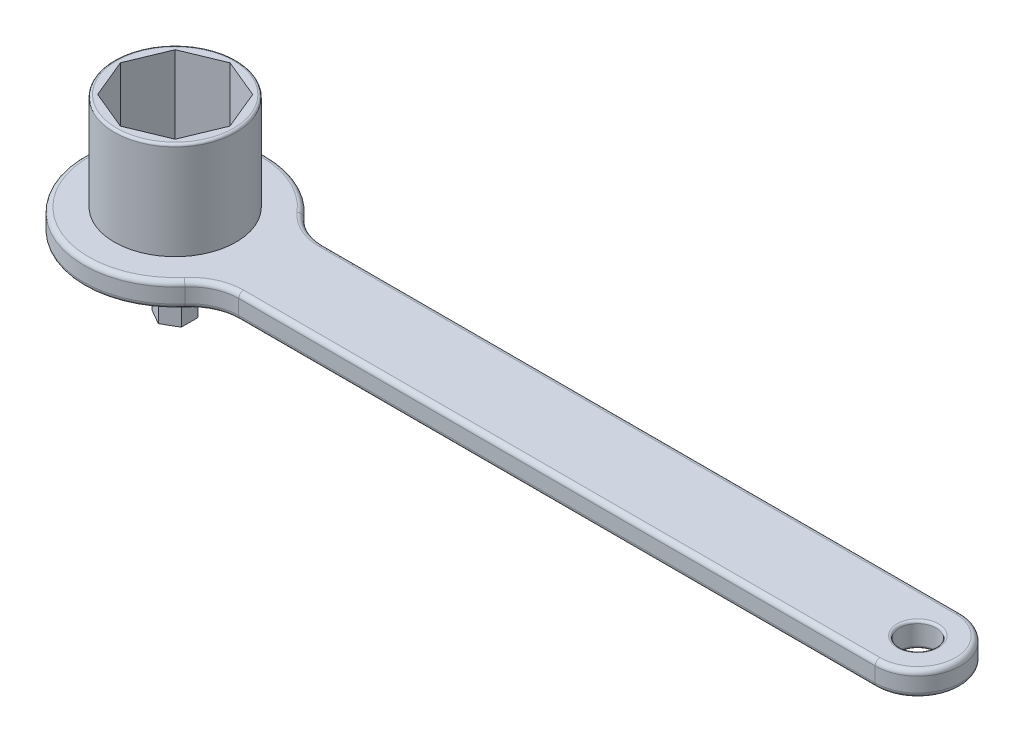
SolidWorks part; units mm, degrees
ref_plane "Front Plane" through (0, 0, 0) normal (0, 0, 1) x (1, 0, 0)
ref_plane "Top Plane" through (0, 0, 0) normal (0, 1, 0) x (1, 0, 0)
ref_plane "Right Plane" through (0, 0, 0) normal (1, 0, 0) x (0, 0, -1)
sketch "Sketch1" plane through (0, 0, 0) normal (0, 1, 0) x (1, 0, 0)
  line L0 (-152.4, 0) -> (152.4, 0) construction
  line L1 (152.4, 17.5) -> (-108.811, 17.5)
  line L2 (152.4, -17.5) -> (-108.811, -17.5)
  arc A0 (-123.9724, 24.4565) -> (-123.9724, -24.4565) centre (-152.4, 0) ccw
  arc A1 (152.4, -17.5) -> (152.4, 17.5) centre (152.4, 0) ccw
  arc A2 (-108.811, -17.5) -> (-123.9724, -24.4565) centre (-108.811, -37.5) ccw
  arc A3 (-108.811, 17.5) -> (-123.9724, 24.4565) centre (-108.811, 37.5) cw
  circle A4 centre (152.4, 0) radius 7.5
  circle A5 centre (-152.4, 0) radius 25
  dimension "D2" = 75
  dimension "D3" = 35
  dimension "D4" = 20
  dimension "D5" = 15
  dimension "D6" = 50
  dimension "D1" = 304.8
extrude "Boss-Extrude1" add sketch "Sketch1" against normal blind 10 contours A5 | L1 A3 A0 A2 L2 A1 A5 A4 region at (-12.9438, 0, 0) region at (-152.4, 0, 0)
extrude "Boss-Extrude2" add sketch "Sketch1<3>" along normal blind 40 contours A5 region at (-152.4, 0, 0)
sketch "Sketch1<3>" plane through (0, 0, 0) normal (0, 1, 0) x (1, 0, 0) same geometry as "Sketch1"
sketch "Sketch2" plane through (0, 40, 0) normal (0, 1, 0) x (1, 0, 0)
  line L0 (-152.4, 22.5) -> (-152.4, -22.5) construction
  line L1 (-129.9, 0) -> (-136.4901, 15.9099)
  line L2 (-136.4901, 15.9099) -> (-152.4, 22.5)
  line L3 (-152.4, 22.5) -> (-168.3099, 15.9099)
  line L4 (-168.3099, 15.9099) -> (-174.9, 0)
  line L5 (-174.9, 0) -> (-168.3099, -15.9099)
  line L6 (-168.3099, -15.9099) -> (-152.4, -22.5)
  line L7 (-152.4, -22.5) -> (-136.4901, -15.9099)
  line L8 (-136.4901, -15.9099) -> (-129.9, 0)
  line L9 (-152.4, 0) -> (-174.9, 0) construction
  line L10 (-152.4, 0) -> (-168.3099, 15.9099) construction
  line L11 (-152.4, 0) -> (-168.3099, -15.9099) construction
  circle A0 centre (-152.4, 0) radius 22.5 construction
  dimension "D1" = 45
  dimension "D2" = 45
extrude "Cut-Extrude1" cut sketch "Sketch2" against normal blind 40
sketch "Sketch3" plane through (0, -10, 0) normal (0, -1, 0) x (1, 0, 0)
  line L0 (-152.4, 15) -> (-152.4, -15) construction
  line L1 (-139.4096, 7.5) -> (-152.4, 15)
  line L2 (-152.4, 15) -> (-165.3904, 7.5)
  line L3 (-165.3904, 7.5) -> (-165.3904, -7.5)
  line L4 (-165.3904, -7.5) -> (-152.4, -15)
  line L5 (-152.4, -15) -> (-139.4096, -7.5)
  line L6 (-139.4096, -7.5) -> (-139.4096, 7.5)
  line L7 (-165.3904, -7.5) -> (-139.4096, 7.5) construction
  circle A1 centre (-152.4, 0) radius 15 construction
  dimension "D1" = 30
  dimension "D2" = 60
  dimension "D3" = 15
extrude "Boss-Extrude3" add sketch "Sketch3" along normal blind 3
sketch "Sketch4" plane through (0, -13, 0) normal (0, -1, 0) x (1, 0, 0)
  line L0 (-152.4, 0) -> (0, 0)
  line L1 (-152.4, 6.925) -> (-158.3972, 3.4625)
  line L2 (-158.3972, 3.4625) -> (-158.3972, -3.4625)
  line L3 (-158.3972, -3.4625) -> (-152.4, -6.925)
  line L4 (-152.4, -6.925) -> (-146.4028, -3.4625)
  line L5 (-146.4028, -3.4625) -> (-146.4028, 3.4625)
  line L6 (-146.4028, 3.4625) -> (-152.4, 6.925)
  line L7 (-152.4, 6.925) -> (-152.4, -6.925) construction
  circle A0 centre (-152.4, 0) radius 6.925 construction
  dimension "D1" = 13.85
  dimension "D2" = 152.4
  dimension "D3" = 11.9945
extrude "Boss-Extrude4" add sketch "Sketch4" along normal blind 25 contours L5 L6 L1 L2 L3 L4 region at (-149.493, -13, 5.0351)
fillet "Fillet1" radius 2 12 edges at (169.9, -10, 0) (-117.1516, -10, -19.3221) (-117.1516, -10, 19.3221) (21.7945, -10, 17.5) (21.7945, -10, -17.5) (-189.9, -10, 0) (-117.1516, 0, -19.3221) (-117.1516, 0, 19.3221) (-189.9, 0, 0) (21.7945, 0, -17.5) (21.7945, 0, 17.5) (169.9, 0, 0)
fillet "Fillet2" radius 1 3 edges at (152.4, -10, 7.5) (152.4, 0, 7.5) (-152.4, 40, 25)
